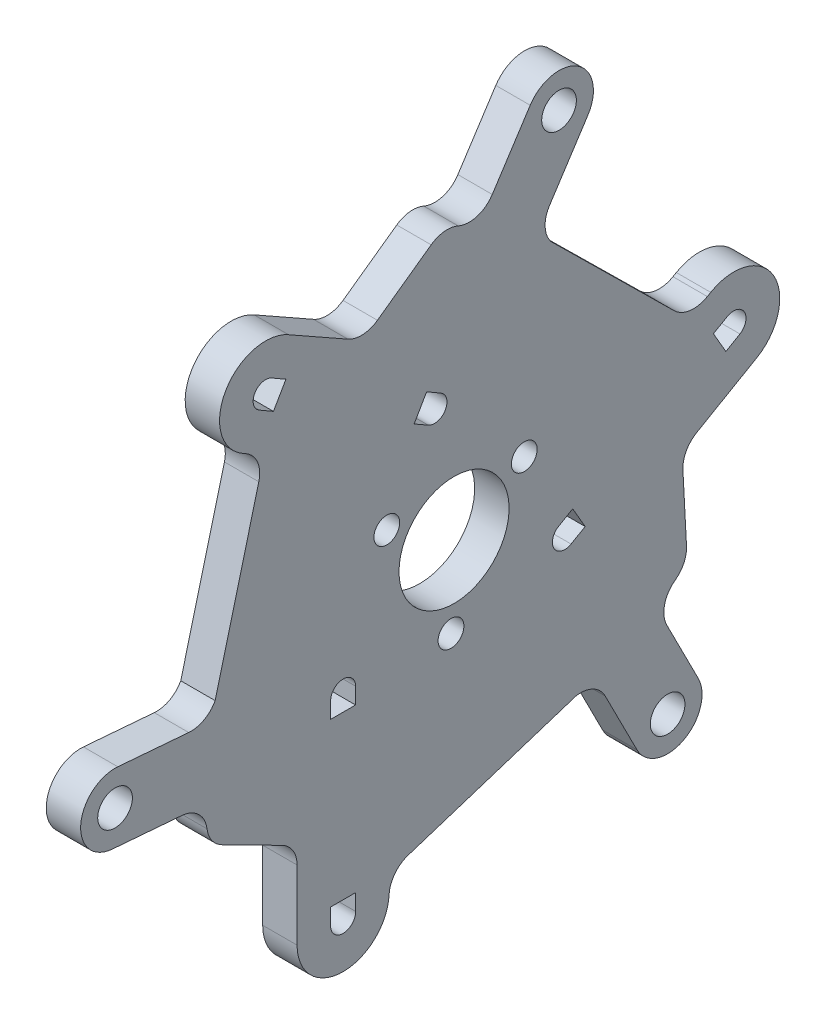
SolidWorks part; units mm, degrees
material "Polyethylene Cross-Linked"
ref_plane "Front Plane" through (0, 0, 0) normal (0, 0, 1) x (1, 0, 0)
ref_plane "Top Plane" through (0, 0, 0) normal (0, 1, 0) x (1, 0, 0)
ref_plane "Right Plane" through (0, 0, 0) normal (1, 0, 0) x (0, 0, -1)
sketch "Sketch1" plane through (0, 0, 0) normal (1, 0, 0) x (0, 0, -1)
  line L0 (0, 0) -> (44.5, 0)
  line L1 (0, 0) -> (22.25, 38.5381)
  line L2 (22.25, 38.5381) -> (44.5, 0)
  line L3 (0.8998, 11.0585) -> (12.8998, 31.8431)
  line L4 (12.8998, 31.8431) -> (22.25, 38.5381)
  line L5 (0.8998, 11.0585) -> (0, 0)
  line L6 (0, 0) -> (10.25, -5.2142)
  line L7 (10.25, -5.2142) -> (34.25, -5.2142)
  line L8 (34.25, -5.2142) -> (44.5, 0)
  line L9 (44.5, 0) -> (43.8906, 11.4838)
  line L10 (43.8906, 11.4838) -> (31.8906, 32.2685)
  line L11 (31.8906, 32.2685) -> (22.25, 38.5381)
  line L12 (22.25, 38.5381) -> (22.25, 0) construction
  line L13 (44.5, 0) -> (11.125, 19.2691) construction
  line L14 (0, 0) -> (33.375, 19.2691) construction
  point P17 (22.25, 12.846)
  dimension "D2" = 44.5
  dimension "D4" = 60
  dimension "D5" = 60
  dimension "D6" = 24
  dimension "D7" = 11.5
  dimension "D8" = 4.75
extrude "Boss-Extrude1" add sketch "Sketch1" along normal blind 3.175 contours L10 L11 L2 L9 | L2 L1 L0 | L3 L5 L1 L4 | L7 L8 L0 L6 region at (0, 12.846, -22.25) region at (0, 20.2511, -9.2231) region at (0, -2.347, -22.25) region at (0, 20.4426, -35.4076)
sketch "Sketch7" plane through (0, 0, 0) normal (-1, 0, 0) x (0, 0, 1)
  circle A0 centre (-22.25, 35.3631) radius 0.7937
  circle A2 centre (-3.1199, 1.927) radius 0.7937
  circle A3 centre (-41.6415, 2.0779) radius 0.7938
  point P8 (-22.3734, 12.7748)
  dimension "D1" = 1.5875
  dimension "D2" = 0
  dimension "D3" = 3.175
  dimension "D4" = 3
sketch "Sketch8" plane through (0, 0, 0) normal (-1, 0, 0) x (0, 0, 1)
  line L0 (-43.8906, 11.4838) -> (-31.8906, 32.2685)
  line L1 (-43.8906, 11.4838) -> (-48.015, 13.8651)
  line L2 (-31.8906, 32.2685) -> (-36.015, 34.6497)
  line L3 (-48.015, 13.8651) -> (-36.015, 34.6497)
  line L8 (-10.25, -5.2142) -> (-34.25, -5.2142)
  line L9 (-10.25, -5.2142) -> (-10.25, -9.9767)
  line L10 (-10.25, -9.9767) -> (-34.25, -9.9767)
  line L11 (-34.25, -5.2142) -> (-34.25, -9.9767)
  line L13 (-8.485, 34.6497) -> (3.515, 13.8651) [skipped]
  line L14 (-0.6094, 11.4838) -> (3.515, 13.8651) [skipped]
  line L15 (-12.6094, 32.2685) -> (-8.485, 34.6497) [skipped]
  line L16 (-12.6094, 32.2685) -> (-0.6094, 11.4838) [skipped]
  line L17 (-12.8998, 31.8431) -> (-0.8998, 11.0585)
  line L18 (-12.8998, 31.8431) -> (-8.7753, 34.2243)
  line L19 (-0.8998, 11.0585) -> (3.2247, 13.4397)
  line L20 (-8.7753, 34.2243) -> (3.2247, 13.4397)
  line L21 (-0.8998, 11.0585) -> (-12.8998, 31.8431) construction
  point P0 (-50.9991, 31.3695)
  point P13 (-22.25, 12.846)
  dimension "D1" = 4.7625
  dimension "D3" = 4.7625
  dimension "D2" = 3
extrude "Boss-Extrude2" add sketch "Sketch8" against normal blind 3.175
sketch "Sketch9" plane through (3.175, 0, 0) normal (1, 0, 0) x (0, 0, -1)
  line L0 (3.4327, 29.558) -> (5.4191, 28.4112)
  line L1 (-3.2247, 13.4397) -> (8.7753, 34.2243) construction
  line L2 (5.4191, 28.4112) -> (8.7753, 34.2243)
  line L3 (8.7753, 34.2243) -> (12.8998, 31.8431)
  line L4 (12.8998, 31.8431) -> (14.5626, 33.0337)
  line L5 (12.8998, 31.8431) -> (22.25, 38.5381) construction
  line L6 (7.6827, 36.9192) -> (14.5626, 33.0337)
  line L7 (8.4625, -12.2704) -> (8.4625, -4.3049)
  line L8 (0, 0) -> (10.25, -5.2142) construction
  line L9 (8.4625, -4.3049) -> (10.25, -5.2142)
  line L10 (10.25, -5.2142) -> (10.25, -9.9767)
  line L15 (16.9625, -10.7704) -> (16.9625, -12.2704)
  line L16 (11.5625, -12.2704) -> (11.5625, -10.7704)
  line L17 (11.5625, -10.7704) -> (13.8625, -10.7703)
  line L18 (13.8625, -10.7703) -> (13.8625, -12.2704)
  line L19 (4.9826, 32.2427) -> (6.2818, 31.4927)
  line L20 (6.2818, 31.4927) -> (7.4317, 33.4845)
  line L21 (7.4317, 33.4845) -> (6.1326, 34.2346)
  line L22 (46.6452, 20.8252) -> (44.6588, 19.6783)
  line L23 (36.015, 34.6497) -> (48.015, 13.8651) construction
  line L24 (50.8952, 13.4639) -> (43.9969, 9.4812)
  line L25 (44.5, 0) -> (43.8906, 11.4838) construction
  line L26 (37.9049, 5.9639) -> (48.2972, 11.9639) construction
  line L27 (43.9969, 9.4812) -> (43.8906, 11.4838)
  line L28 (43.8906, 11.4838) -> (48.015, 13.8651)
  line L29 (48.015, 13.8651) -> (44.6588, 19.6783)
  line L30 (48.1952, 18.1405) -> (46.8961, 17.3904)
  line L31 (46.8961, 17.3904) -> (48.0462, 15.3982)
  line L32 (46.4641, 18.1387) -> (48.478, 14.6501) construction
  line L33 (48.0462, 15.3982) -> (49.3452, 16.1486)
  line L35 (16.9625, -10.7704) -> (20.6064, -10.7704)
  line L36 (10.25, -9.4292) -> (10.25, -9.9767)
  line L37 (20.6064, -10.7704) -> (20.6064, -9.9767)
  line L38 (34.25, -9.9767) -> (10.25, -9.9767) construction
  line L39 (20.6064, -9.9767) -> (10.25, -9.9767)
  arc A0 (3.4327, 29.558) -> (7.6827, 36.9192) centre (5.5577, 33.2386) cw
  arc A1 (16.9625, -12.2704) -> (8.4625, -12.2704) centre (12.7125, -12.2704) cw
  arc A2 (11.5625, -12.2704) -> (13.8625, -12.2704) centre (12.7125, -12.3069) ccw
  arc A3 (4.9826, 32.2427) -> (6.1326, 34.2346) centre (5.5576, 33.2386) cw
  arc A4 (46.6452, 20.8252) -> (50.8952, 13.4639) centre (48.7702, 17.1445) cw
  arc A5 (48.1952, 18.1405) -> (49.3452, 16.1486) centre (48.7544, 17.1354) cw
  point P16 (7.6827, 36.9192)
extrude "Boss-Extrude3" add sketch "Sketch9" against normal blind 3.175 contours L6 L4 L3 L2 L0 A0 | L29 L22 A4 L24 L27 L28 | L39 L37 L35 L15 A1 L7 L9 L10 | L33 A5 L30 L31 | L21 A3 L19 L20 | A2 L18 L17 L16
sketch "Sketch12" plane through (3.175, 0, 0) normal (1, 0, 0) x (0, 0, -1)
  line L0 (33.7568, 7.1486) -> (35.0559, 7.8987)
  line L1 (35.0559, 7.8987) -> (33.9059, 9.8905)
  line L2 (33.9059, 9.8905) -> (32.6068, 9.1405)
  line L3 (21.7211, 25.2346) -> (20.422, 25.9846)
  line L4 (20.422, 25.9846) -> (19.272, 23.9928)
  line L5 (20.8539, 26.7331) -> (18.84, 23.2445) construction
  line L6 (19.272, 23.9928) -> (20.5711, 23.2427)
  line L7 (13.8625, 5.7296) -> (13.8625, 4.2295)
  line L8 (13.8625, 4.2295) -> (11.5625, 4.2295)
  line L9 (11.5625, 4.2295) -> (11.5625, 5.7296)
  arc A0 (32.6068, 9.1405) -> (33.7568, 7.1486) centre (33.1818, 8.1446) ccw
  arc A1 (11.5625, 5.7296) -> (13.8625, 5.7296) centre (12.7125, 5.7296) cw
  arc A2 (20.5711, 23.2427) -> (21.7211, 25.2346) centre (21.1461, 24.2386) ccw
extrude "Cut-Extrude8" cut sketch "Sketch12" against normal blind 3.175
sketch "Sketch10" plane through (3.175, 0, 0) normal (1, 0, 0) x (0, 0, -1)
  line L0 (31.8906, 32.2685) -> (44.6588, 19.6783)
  line L1 (44.6588, 19.6783) -> (36.015, 34.6497)
  line L2 (36.015, 34.6497) -> (31.8906, 32.2685)
  line L3 (5.4191, 28.4112) -> (0.8998, 11.0585)
  line L4 (0.8998, 11.0585) -> (-3.2247, 13.4397)
  line L5 (-3.2247, 13.4397) -> (5.4191, 28.4112)
  line L11 (16.9625, -10.7704) -> (34.25, -5.2142)
  line L12 (34.25, -5.2142) -> (34.25, -11.4141)
  line L13 (34.25, -11.4141) -> (16.9625, -10.7704)
extrude "Cut-Extrude7" cut sketch "Sketch10" against normal blind 3.175
fillet "Fillet1" radius 2.54 1 edges at (1.5875, -10.7704, -16.9625)
fillet "Fillet2" radius 2.54 8 edges at (1.5875, 9.4812, -43.9969) (1.5875, 0, -44.5) (1.5875, 19.6783, -44.6588) (1.5875, 38.5381, -22.25) (1.5875, 33.0337, -14.5626) (1.5875, 28.4112, -5.4191) (1.5875, 0, 0) (1.5875, -4.3049, -8.4625)
sketch "Sketch13" plane through (0, 0, 0) normal (-1, 0, 0) x (0, 0, 1)
  line L0 (-34.25, -5.2142) -> (-18.716, -10.2068) construction
  line L1 (-29.4368, 16.2939) -> (-22.6725, 5.5452)
  line L2 (-22.6725, 5.5452) -> (-16.746, 16.7775)
  line L3 (-16.746, 16.7775) -> (-29.4368, 16.2939)
  circle A0 centre (-22.9518, 12.8722) radius 3.6662 construction
  circle A2 centre (-22.6725, 5.5452) radius 1.1906
  circle A3 centre (-29.4368, 16.2939) radius 1.1906
  circle A4 centre (-16.746, 16.7775) radius 1.1906
  point P8 (-22.9518, 12.8722)
  dimension "D2" = 2.3813
  dimension "D1" = 12.7
  dimension "D3" = 80
extrude "Cut-Extrude9" cut sketch "Sketch13" against normal blind 3.175 contours L2 A4 L3 | L3 A4 L2 | A2 | A3 region at (0, 16.8583, -16.6177) region at (0, 16.3738, -17.3875)
sketch "Sketch17" plane through (0, 0, 0) normal (-1, 0, 0) x (0, 0, 1)
  line L0 (-35.809, -4.4211) -> (-39.8397, -12.3448)
  line L1 (-34.25, -5.2142) -> (-43.0277, -0.749) construction
  line L2 (-41.4687, -1.542) -> (-45.4995, -9.4657)
  line L3 (-35.809, -4.4211) -> (-41.4687, -1.542)
  line L4 (-0.2615, 3.2135) -> (8.5992, 3.9345)
  line L5 (-0.8998, 11.0585) -> (-0.1381, 1.6976) construction
  line L6 (-0.7764, 9.5426) -> (8.0843, 10.2636)
  line L7 (-0.2615, 3.2135) -> (-0.7764, 9.5426)
  line L8 (-25.1355, 36.6616) -> (-29.9822, 44.1142)
  line L9 (-31.8906, 32.2685) -> (-23.7036, 37.5928) construction
  line L10 (-30.4588, 33.1996) -> (-35.3055, 40.6522)
  line L11 (-25.1355, 36.6616) -> (-30.4588, 33.1996)
  arc A0 (-39.8397, -12.3448) -> (-45.4995, -9.4657) centre (-42.6696, -10.9053) cw
  circle A1 centre (-42.6696, -10.9053) radius 1.6
  arc A2 (8.5992, 3.9345) -> (8.0843, 10.2636) centre (8.3418, 7.099) ccw
  circle A3 centre (8.3418, 7.099) radius 1.6
  arc A4 (-29.9822, 44.1142) -> (-35.3055, 40.6522) centre (-32.6439, 42.3832) ccw
  circle A5 centre (-32.6439, 42.3832) radius 1.6
  point P8 (-38.6388, -2.9816)
  point P16 (-0.519, 6.3781)
  point P27 (-27.7971, 34.9306)
  dimension "D2" = 3.175
  dimension "D3" = 3.2
  dimension "D1" = 8.89
extrude "Boss-Extrude5" add sketch "Sketch17" against normal up to surface (3.175 mm away) up to face at (3.175, 16.7775, -15.5554)
fillet "Fillet4" radius 2.54 6 edges at (1.5875, 36.6616, -25.1355) (1.5875, 33.1996, -30.4588) (1.5875, -1.542, -41.4687) (1.5875, -4.4211, -35.809) (1.5875, 9.5426, -0.7764) (1.5875, 3.2135, -0.2615)
sketch "Sketch20" plane through (0, 0, 0) normal (-1, 0, 0) x (0, 0, 1)
  circle A0 centre (-22.9518, 12.8722) radius 5.08
  circle A1 centre (-22.9518, 12.8722) radius 8.523 construction
  circle A4 centre (-16.746, 16.7775) radius 1.1906 construction
  circle A5 centre (-29.4368, 16.2939) radius 1.1906 construction
  circle A6 centre (-22.6725, 5.5452) radius 1.1906 construction
  dimension "D1" = 10.16
extrude "Cut-Extrude12" cut sketch "Sketch20" against normal through all
sketch "Sketch23" plane through (3.175, 0, 0) normal (1, 0, 0) x (0, 0, -1)
  line L0 (22.9518, 12.8722) -> (22.25, 35.3631)
  circle A0 centre (22.9518, 12.8722) radius 5.08 construction
  circle A1 centre (22.9518, 12.8722) radius 5.08
equation "\"HOLE_SIZE\"= 3.2mm"
